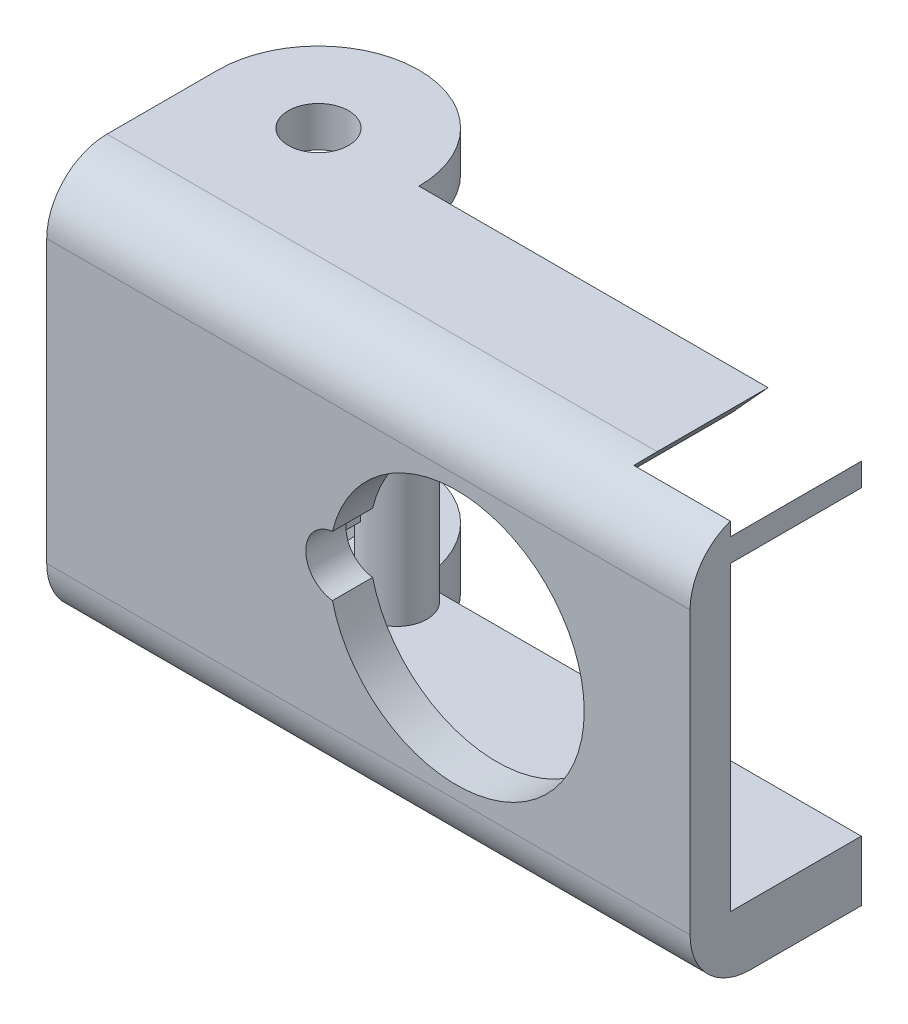
SolidWorks part; units mm, degrees
ref_plane "Front Plane" through (0, 0, 0) normal (0, 0, 1) x (1, 0, 0)
ref_plane "Top Plane" through (0, 0, 0) normal (0, 1, 0) x (1, 0, 0)
ref_plane "Right Plane" through (0, 0, 0) normal (1, 0, 0) x (0, 0, -1)
sketch "Sketch1" plane through (0, 0, 0) normal (0, 1, 0) x (1, 0, 0)
  line L0 (0, 0) -> (0, -8.515) construction
  line L1 (-5, -8.515) -> (5, -8.515)
  line L2 (5, -8.515) -> (5, 0)
  line L3 (-5, 0) -> (-5, -8.515)
  arc A0 (5, 0) -> (-5, 0) centre (0, 0) ccw
  circle A1 centre (0, 0) radius 1.5
  point P8 (0, -8.515)
  dimension "D1" = 3
  dimension "D2" = 10
extrude "Boss-Extrude1" add sketch "Sketch1" along normal blind 10 and the other way blind 10
sketch "Sketch2" plane through (0, 0, 0) normal (1, 0, 0) x (0, 0, -1)
  line L0 (5, -10) -> (5, 10) construction
  line L1 (5, 8) -> (-4.1592, 8)
  line L2 (5, 8) -> (5, 4)
  line L3 (5, 4) -> (-4.1592, 4)
  line L4 (-4.1592, 8) -> (-4.1592, 4)
  line L5 (-4.1592, 10) -> (-4.1592, -10) construction
  line L6 (5, 2.5) -> (-4.1592, 2.5)
  line L7 (5, 2.5) -> (5, -1.5)
  line L8 (5, -1.5) -> (-4.1592, -1.5)
  line L9 (-4.1592, 2.5) -> (-4.1592, -1.5)
  line L10 (5, -3) -> (-4.1592, -3)
  line L11 (5, -3) -> (5, -7)
  line L12 (5, -7) -> (-4.1592, -7)
  line L13 (-4.1592, -3) -> (-4.1592, -7)
  line L14 (-8.515, 10) -> (0, 10) construction
  line L15 (-8.515, -10) -> (0, -10) construction
  dimension "D1" = 4
  dimension "D2" = 2
  dimension "D3" = 1.5
  dimension "D4" = 1.5
extrude "Cut-Extrude1" cut sketch "Sketch2" against normal through all both and the other way through all
fillet "Fillet1" radius 3 2 edges at (0, -10, 8.515) (0, 10, 8.515)
sketch "Sketch3" plane through (5, 0, 0) normal (1, 0, 0) x (0, 0, -1)
  line L0 (-4.1592, 8) -> (-6.515, 8)
  line L1 (-6.515, 8) -> (-6.515, -7)
  line L2 (-6.515, -7) -> (-4.1592, -7)
  line L16 (-8.515, 7) -> (-8.515, -7)
  line L17 (-5.515, -10) -> (0, -10)
  line L18 (0, -10) -> (0, -7)
  line L19 (0, -7) -> (-4.1592, -7)
  line L20 (-4.1592, -7) -> (-4.1592, -3)
  line L21 (-4.1592, -3) -> (0, -3)
  line L22 (0, -3) -> (0, -1.5)
  line L23 (0, -1.5) -> (-4.1592, -1.5)
  line L24 (-4.1592, -1.5) -> (-4.1592, 2.5)
  line L25 (-4.1592, 2.5) -> (0, 2.5)
  line L26 (0, 2.5) -> (0, 4)
  line L27 (0, 4) -> (-4.1592, 4)
  line L28 (-4.1592, 4) -> (-4.1592, 8)
  line L29 (-4.1592, 8) -> (0, 8)
  line L30 (0, 8) -> (0, 10)
  line L31 (0, 10) -> (-5.515, 10)
  line L32 (-8.515, 7) -> (-8.515, -7)
  line L33 (-5.515, -10) -> (0, -10)
  line L34 (0, -10) -> (0, -7)
  line L35 (0, -7) -> (-4.1592, -7)
  line L45 (-4.1592, 8) -> (0, 8)
  line L46 (0, 8) -> (0, 10)
  line L47 (0, 10) -> (-5.515, 10)
  arc A2 (-8.515, -7) -> (-5.515, -10) centre (-5.515, -7) ccw
  arc A3 (-5.515, 10) -> (-8.515, 7) centre (-5.515, 7) ccw
  arc A4 (-8.515, -7) -> (-5.515, -10) centre (-5.515, -7) ccw
  arc A5 (-5.515, 10) -> (-8.515, 7) centre (-5.515, 7) ccw
  dimension "D2" = 2
  dimension "D1" = 0
extrude "Boss-Extrude2" add sketch "Sketch3" along normal blind 22
sketch "Sketch4" plane through (0, 0, 6.515) normal (0, 0, -1) x (-1, 0, 0)
  line L0 (0, 0) -> (-15.3836, 0) construction
  arc A0 (-9.2109, 1.49) -> (-9.2109, -1.49) centre (-15.3836, 0) ccw
  arc A1 (-9.2109, -1.49) -> (-9.2109, 1.49) centre (-9.3836, 0) ccw
  dimension "D1" = 12.7
  dimension "D2" = 3
  dimension "D3" = 6
extrude "Cut-Extrude2" cut sketch "Sketch4" against normal blind 15
sketch "Sketch6" plane through (0, 0, 6.515) normal (0, 0, -1) x (-1, 0, 0)
  line L0 (0, 0) -> (-15.3836, 0) construction
  line L1 (-15.3836, 0) -> (-28.9619, 14.8955) construction
  line L2 (-22.0368, 3.705) -> (-28.5739, 10.8763)
  line L3 (-22.0368, 3.705) -> (-19.0807, 6.3997)
  line L4 (-28.5739, 10.8763) -> (-25.6178, 13.571)
  line L5 (-19.0807, 6.3997) -> (-25.6178, 13.571)
  line L6 (-22.0368, 3.705) -> (-25.6178, 13.571) construction
  line L7 (-28.5739, 10.8763) -> (-19.0807, 6.3997) construction
  line L8 (-5, 8) -> (-5, 4) construction
  line L9 (-5, 8) -> (-5, 4) construction
  point P6 (-23.8273, 8.638)
extrude "Cut-Extrude3" cut sketch "Sketch6" along normal blind 15
sketch "Sketch7" plane through (0, 8, 0) normal (0, -1, 0) x (1, 0, 0)
  circle A0 centre (5.3584, 1.4565) radius 1.5
  dimension "D1" = 3
extrude "Boss-Extrude3" add sketch "Sketch7" along normal blind 17
